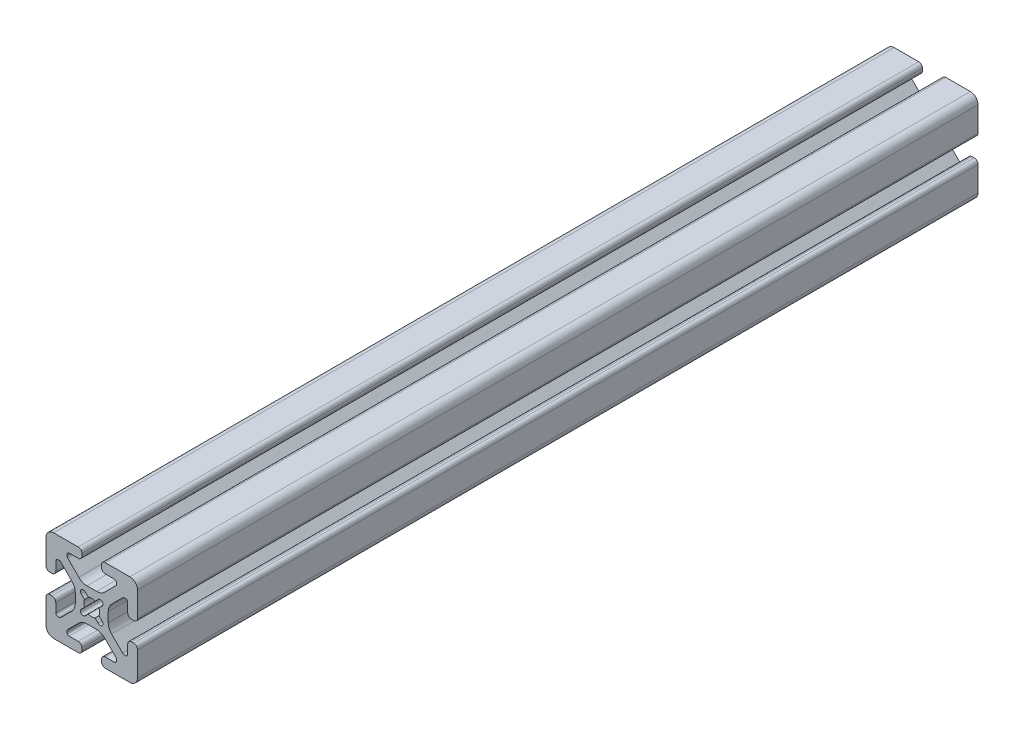
SolidWorks part; units mm, degrees
material "6061-T6 (SS)"
ref_plane "Front Plane" through (0, 0, 0) normal (0, 0, 1) x (1, 0, 0)
ref_plane "Top Plane" through (0, 0, 0) normal (0, 1, 0) x (1, 0, 0)
ref_plane "Right Plane" through (0, 0, 0) normal (1, 0, 0) x (0, 0, -1)
sketch "Sketch1" plane through (0, 0, 0) normal (0, 0, 1) x (1, 0, 0)
  line L0 (4.2456, 2.6398) -> (3.0178, 1.4017)
  line L1 (3.0179, -1.4014) -> (4.3433, -2.7269)
  line L2 (2.7269, -4.3433) -> (1.4014, -3.0179)
  line L3 (-1.4014, -3.0179) -> (-2.7269, -4.3433)
  line L4 (-4.3433, -2.7269) -> (-3.0179, -1.4014)
  line L5 (-3.0179, 1.4014) -> (-4.3433, 2.7269)
  line L6 (-2.7269, 4.3433) -> (-1.4014, 3.0179)
  line L7 (1.4017, 3.0178) -> (2.6398, 4.2456)
  line L8 (14.986, -5.6388) -> (14.986, -9.398)
  line L9 (14.097, -10.287) -> (13.5289, -10.287)
  line L10 (12.9003, -10.0266) -> (8.2608, -5.3872)
  line L11 (6.8697, -2.0285) -> (6.8697, 2.0285)
  line L12 (8.2608, 5.3872) -> (12.9003, 10.0266)
  line L13 (13.5289, 10.287) -> (14.097, 10.287)
  line L14 (14.986, 9.398) -> (14.986, 5.6388)
  line L15 (16.5608, 4.064) -> (17.4752, 4.064)
  line L16 (19.05, 5.6388) -> (19.05, 15.875)
  line L17 (15.875, 19.05) -> (5.6388, 19.05)
  line L18 (4.064, 17.4752) -> (4.064, 16.5608)
  line L19 (5.6388, 14.986) -> (9.398, 14.986)
  line L20 (10.287, 14.097) -> (10.287, 13.5289)
  line L21 (10.0266, 12.9003) -> (5.3872, 8.2608)
  line L22 (2.0285, 6.8697) -> (-2.0285, 6.8697)
  line L23 (-5.3872, 8.2608) -> (-10.0266, 12.9003)
  line L24 (-10.287, 13.5289) -> (-10.287, 14.097)
  line L25 (-9.398, 14.986) -> (-5.6388, 14.986)
  line L26 (-4.064, 16.5608) -> (-4.064, 17.4752)
  line L27 (-5.6388, 19.05) -> (-15.875, 19.05)
  line L28 (-19.05, 15.875) -> (-19.05, 5.6388)
  line L29 (-17.4752, 4.064) -> (-16.5608, 4.064)
  line L30 (-14.986, 5.6388) -> (-14.986, 9.398)
  line L31 (-14.097, 10.287) -> (-13.5289, 10.287)
  line L32 (-12.9003, 10.0266) -> (-8.2608, 5.3872)
  line L33 (-6.8697, 2.0285) -> (-6.8697, -2.0285)
  line L34 (-8.2608, -5.3872) -> (-12.9003, -10.0266)
  line L35 (-13.5289, -10.287) -> (-14.097, -10.287)
  line L36 (-14.986, -9.398) -> (-14.986, -5.6388)
  line L37 (-16.5608, -4.064) -> (-17.4752, -4.064)
  line L38 (-19.05, -5.6388) -> (-19.05, -15.875)
  line L39 (-15.875, -19.05) -> (-5.6388, -19.05)
  line L40 (-4.064, -17.4752) -> (-4.064, -16.5608)
  line L41 (-5.6388, -14.986) -> (-9.398, -14.986)
  line L42 (-10.287, -14.097) -> (-10.287, -13.5289)
  line L43 (-10.0266, -12.9003) -> (-5.3872, -8.2608)
  line L44 (-2.0285, -6.8697) -> (2.0285, -6.8697)
  line L45 (5.3872, -8.2608) -> (10.0266, -12.9003)
  line L46 (10.287, -13.5289) -> (10.287, -14.097)
  line L47 (9.398, -14.986) -> (5.6388, -14.986)
  line L48 (4.064, -16.5608) -> (4.064, -17.4752)
  line L49 (5.6388, -19.05) -> (15.875, -19.05)
  line L50 (19.05, -15.875) -> (19.05, -5.6388)
  line L51 (17.4752, -4.064) -> (16.5608, -4.064)
  arc A0 (4.2456, 2.6398) -> (2.6398, 4.2456) centre (3.5351, 3.5351) ccw
  arc A1 (1.4017, 3.0178) -> (-1.4014, 3.0179) centre (0, 0) ccw
  arc A2 (2.7269, -4.3433) -> (4.3433, -2.7269) centre (3.5351, -3.5351) ccw
  arc A3 (-3.0179, 1.4014) -> (-3.0179, -1.4014) centre (0, 0) ccw
  arc A4 (-4.3433, -2.7269) -> (-2.7269, -4.3433) centre (-3.5351, -3.5351) ccw
  arc A5 (-1.4014, -3.0179) -> (1.4014, -3.0179) centre (0, 0) ccw
  arc A6 (-2.7269, 4.3433) -> (-4.3433, 2.7269) centre (-3.5351, 3.5351) ccw
  arc A8 (16.5608, -4.064) -> (14.986, -5.6388) centre (16.5608, -5.6388) ccw
  arc A9 (14.097, -10.287) -> (14.986, -9.398) centre (14.097, -9.398) ccw
  arc A10 (12.9003, -10.0266) -> (13.5289, -10.287) centre (13.5289, -9.398) ccw
  arc A11 (6.8697, -2.0285) -> (8.2608, -5.3872) centre (11.6195, -2.0285) ccw
  arc A12 (8.2608, 5.3872) -> (6.8697, 2.0285) centre (11.6195, 2.0285) ccw
  arc A13 (13.5289, 10.287) -> (12.9003, 10.0266) centre (13.5289, 9.398) ccw
  arc A14 (14.986, 9.398) -> (14.097, 10.287) centre (14.097, 9.398) ccw
  arc A15 (14.986, 5.6388) -> (16.5608, 4.064) centre (16.5608, 5.6388) ccw
  arc A16 (17.4752, 4.064) -> (19.05, 5.6388) centre (17.4752, 5.6388) ccw
  arc A17 (19.05, 15.875) -> (15.875, 19.05) centre (15.875, 15.875) ccw
  arc A18 (5.6388, 19.05) -> (4.064, 17.4752) centre (5.6388, 17.4752) ccw
  arc A19 (4.064, 16.5608) -> (5.6388, 14.986) centre (5.6388, 16.5608) ccw
  arc A20 (10.287, 14.097) -> (9.398, 14.986) centre (9.398, 14.097) ccw
  arc A21 (10.0266, 12.9003) -> (10.287, 13.5289) centre (9.398, 13.5289) ccw
  arc A22 (2.0285, 6.8697) -> (5.3872, 8.2608) centre (2.0285, 11.6195) ccw
  arc A23 (-5.3872, 8.2608) -> (-2.0285, 6.8697) centre (-2.0285, 11.6195) ccw
  arc A24 (-10.287, 13.5289) -> (-10.0266, 12.9003) centre (-9.398, 13.5289) ccw
  arc A25 (-9.398, 14.986) -> (-10.287, 14.097) centre (-9.398, 14.097) ccw
  arc A26 (-5.6388, 14.986) -> (-4.064, 16.5608) centre (-5.6388, 16.5608) ccw
  arc A27 (-4.064, 17.4752) -> (-5.6388, 19.05) centre (-5.6388, 17.4752) ccw
  arc A28 (-15.875, 19.05) -> (-19.05, 15.875) centre (-15.875, 15.875) ccw
  arc A29 (-19.05, 5.6388) -> (-17.4752, 4.064) centre (-17.4752, 5.6388) ccw
  arc A30 (-16.5608, 4.064) -> (-14.986, 5.6388) centre (-16.5608, 5.6388) ccw
  arc A31 (-14.097, 10.287) -> (-14.986, 9.398) centre (-14.097, 9.398) ccw
  arc A32 (-12.9003, 10.0266) -> (-13.5289, 10.287) centre (-13.5289, 9.398) ccw
  arc A33 (-6.8697, 2.0285) -> (-8.2608, 5.3872) centre (-11.6195, 2.0285) ccw
  arc A34 (-8.2608, -5.3872) -> (-6.8697, -2.0285) centre (-11.6195, -2.0285) ccw
  arc A35 (-13.5289, -10.287) -> (-12.9003, -10.0266) centre (-13.5289, -9.398) ccw
  arc A36 (-14.986, -9.398) -> (-14.097, -10.287) centre (-14.097, -9.398) ccw
  arc A37 (-14.986, -5.6388) -> (-16.5608, -4.064) centre (-16.5608, -5.6388) ccw
  arc A38 (-17.4752, -4.064) -> (-19.05, -5.6388) centre (-17.4752, -5.6388) ccw
  arc A39 (-19.05, -15.875) -> (-15.875, -19.05) centre (-15.875, -15.875) ccw
  arc A40 (-5.6388, -19.05) -> (-4.064, -17.4752) centre (-5.6388, -17.4752) ccw
  arc A41 (-4.064, -16.5608) -> (-5.6388, -14.986) centre (-5.6388, -16.5608) ccw
  arc A42 (-10.287, -14.097) -> (-9.398, -14.986) centre (-9.398, -14.097) ccw
  arc A43 (-10.0266, -12.9003) -> (-10.287, -13.5289) centre (-9.398, -13.5289) ccw
  arc A44 (-2.0285, -6.8697) -> (-5.3872, -8.2608) centre (-2.0285, -11.6195) ccw
  arc A45 (5.3872, -8.2608) -> (2.0285, -6.8697) centre (2.0285, -11.6195) ccw
  arc A46 (10.287, -13.5289) -> (10.0266, -12.9003) centre (9.398, -13.5289) ccw
  arc A47 (9.398, -14.986) -> (10.287, -14.097) centre (9.398, -14.097) ccw
  arc A48 (5.6388, -14.986) -> (4.064, -16.5608) centre (5.6388, -16.5608) ccw
  arc A49 (4.064, -17.4752) -> (5.6388, -19.05) centre (5.6388, -17.4752) ccw
  arc A50 (15.875, -19.05) -> (19.05, -15.875) centre (15.875, -15.875) ccw
  arc A51 (19.05, -5.6388) -> (17.4752, -4.064) centre (17.4752, -5.6388) ccw
  arc A52 (3.0179, -1.4014) -> (3.0178, 1.4017) centre (0, 0) ccw
  dimension "D1" = 6.6548
extrude "Extrude1" add sketch "Sketch1" against normal blind 350
ref_plane "Plane1" through (0, 0, 0) normal (0, 1, 0) x (1, 0, 0)
